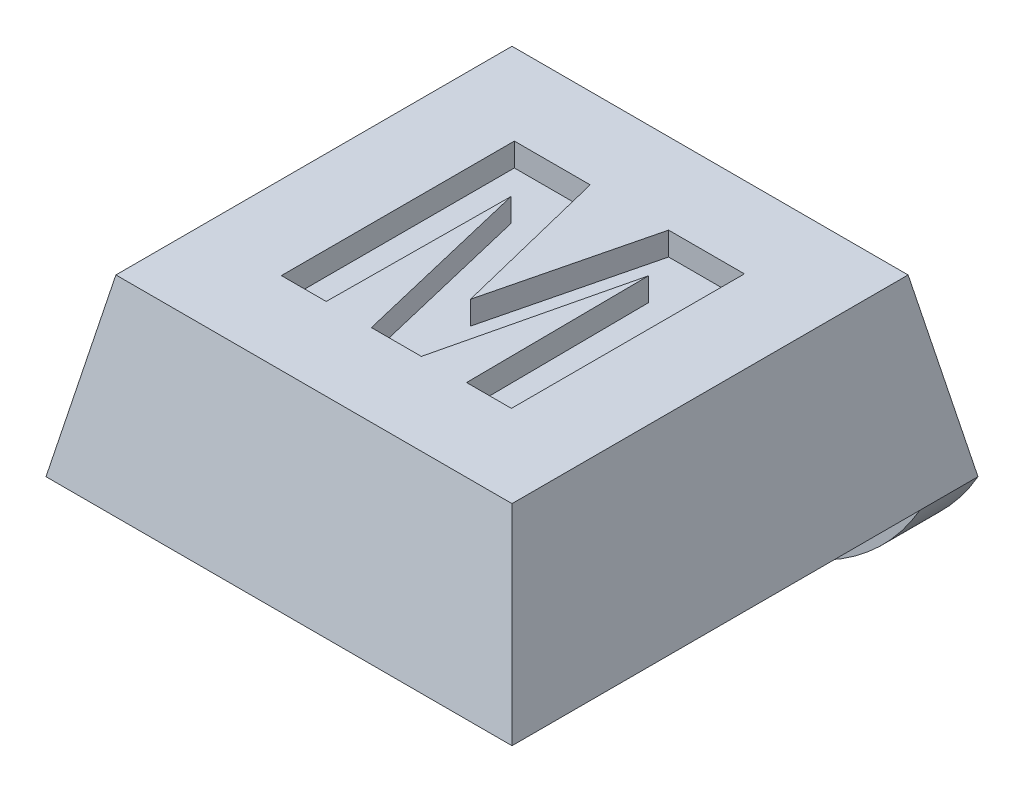
SolidWorks part; units mm, degrees
ref_plane "Front Plane" through (0, 0, 0) normal (0, 0, 1) x (1, 0, 0)
ref_plane "Top Plane" through (0, 0, 0) normal (0, 1, 0) x (1, 0, 0)
ref_plane "Right Plane" through (0, 0, 0) normal (1, 0, 0) x (0, 0, -1)
sketch "Sketch1" plane through (0, 0, 0) normal (0, 1, 0) x (1, 0, 0)
  line L1 (0, 0) -> (8, 0)
  line L2 (0, 0) -> (0, 8)
  line L3 (0, 8) -> (8, 8)
  line L4 (8, 0) -> (8, 8)
  dimension "D1" = 8
  dimension "D2" = 8
extrude "Boss-Extrude1" add sketch "Sketch1" along normal blind 3
sketch "Sketch2" plane through (0, 0, 0) normal (0, 0, 1) x (1, 0, 0)
  line L0 (0, 0) -> (0.6, 3)
  line L1 (0, 3) -> (8, 3) construction
  line L2 (0.6, 3) -> (0, 3)
  line L3 (0, 3) -> (0, 0)
  line L4 (8, 0) -> (7.4, 3)
  line L5 (7.4, 3) -> (8, 3)
  line L6 (8, 3) -> (8, 0)
  dimension "D1" = 0.6
  dimension "D2" = 0.6
extrude "Cut-Extrude1" cut sketch "Sketch2" against normal through all both and the other way through all
sketch "Sketch3" plane through (0, 0, 0) normal (1, 0, 0) x (0, 0, -1)
  line L0 (0, 0) -> (0.6, 3)
  line L1 (8, 3) -> (0, 3) construction
  line L2 (0.6, 3) -> (0, 3)
  line L3 (0, 3) -> (0, 0)
  line L4 (8, 3) -> (7.4, 3)
  line L5 (7.4, 3) -> (8, 0)
  line L6 (8, 3) -> (8, 0)
  dimension "D1" = 0.6
  dimension "D2" = 0.6
extrude "Cut-Extrude2" cut sketch "Sketch3" along normal blind 11
sketch "Sketch4" plane through (0, 0, 0) normal (0, -1, 0) x (1, 0, 0)
  line L0 (8, 0) -> (8, -8) construction
  line L3 (0, 0) -> (8, 0) construction
  circle A0 centre (4, -3.75) radius 1.75
  dimension "D1" = 3.5
  dimension "D2" = 4
  dimension "D3" = 3.75
extrude "Cut-Extrude3" cut sketch "Sketch4" against normal blind 0.4
sketch "Sketch5" plane through (0, 0, 0) normal (0, -1, 0) x (1, 0, 0)
  line L0 (8, 0) -> (8, -8) construction
  line L1 (0, -8) -> (8, -8)
  line L2 (0, -8) -> (0, -7)
  line L3 (0, -7) -> (8, -7)
  line L4 (8, -8) -> (8, -7)
  dimension "D1" = 1
extrude "Boss-Extrude2" add sketch "Sketch5" along normal blind 2
fillet "Fillet1" radius 4 2 edges at (8, -2, -7.5) (0, -2, -7.5)
sketch "Sketch6" plane through (0, 3, 0) normal (0, 1, 0) x (1, 0, 0)
  text T0 "M" font "Arial" height 4
extrude "Cut-Extrude4" cut sketch "Sketch6" against normal blind 0.4
